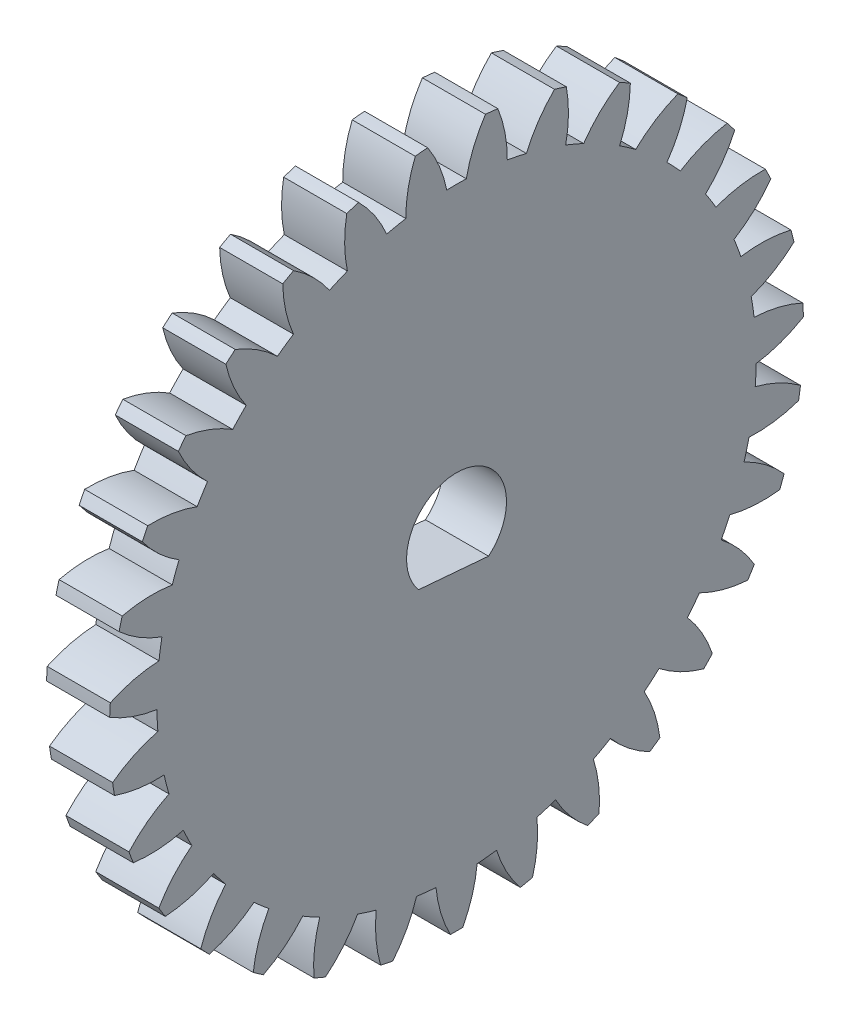
SolidWorks part; units mm, degrees
ref_plane "Plane1" through (0, 0, 0) normal (0, 0, 1) x (1, 0, 0)
ref_plane "Plane2" through (0, 0, 0) normal (0, 1, 0) x (1, 0, 0)
ref_plane "Plane3" through (0, 0, 0) normal (1, 0, 0) x (0, 0, -1)
sketch "HoldingSke" plane through (0, 0, 0) normal (0, 1, 0) x (1, 0, 0)
  line L0 (0, 0) -> (0.8572, -0.515)
  line L1 (-15, 0) -> (100, 0) construction
  line L2 (0, 0) -> (-2.1039, 2.3779)
  line L3 (0, 0) -> (-11.863, 4.5341)
  line L4 (0, 0) -> (7.4025, 4.4479)
  line L5 (0, 0) -> (-46.8476, -17.4728)
  line L6 (0, 0) -> (-1.6579, -1.1186)
  line L7 (-2.1039, 2.3779) -> (8.6586, 51.2059)
  line L8 (-76.2, 54.61) -> (-76.1, 54.61)
  line L9 (-71.009, 38.7566) -> (-53.1078, 45.2721)
  line L10 (-76.2, 71.12) -> (104.1128, 71.12)
  line L11 (0, 0) -> (-2, 0)
  line L12 (-76.2, 101.6) -> (-76.162, 101.6)
  line L13 (24.9733, 27.94) -> (52.9518, 28.4284)
  line L14 (24.9733, 27.94) -> (24.9743, 27.94)
  line L15 (24.9733, 27.94) -> (100.4006, 29.5858)
  line L16 (-63.627, -1) -> (-12.827, -1)
  circle A0 centre (0, 0) radius 0.5
  circle A1 centre (0, 0) radius 14.249
  circle A2 centre (0, 0) radius 37.5
  circle A3 centre (0, 0) radius 0.5
  dimension "MHD" = 28.498
  dimension "Hub_dia" = 75
  dimension "Bore" = 1
  dimension "MBD" = 1
  dimension "Num_teeth" = 31
  dimension "Pitch" = 1
  dimension "Overall_len" = 50
  dimension "Show_teeth" = 31
  dimension "Thickness" = 2
  dimension "OAL" = 50.0001
  dimension "T_dim" = 0.1
  dimension "Ap" = 20
  dimension "H" = 19.05
  dimension "Pitch_radius" = 180.3128
  dimension "Width" = 2
  dimension "Backlash" = 0.038
  dimension "Addendum_fac" = 1
  dimension "Dedendum_fac" = 1.25
  dimension "Clearance_fac" = 0.25
  dimension "Dedendum_add" = 0.001
  dimension "Module" = 1
sketch "BasProSke" plane through (0, 0, 0) normal (0, 1, 0) x (1, 0, 0)
  line L0 (-10, 0) -> (60, 0) construction
  line L1 (0, 0) -> (0, 16.5)
  line L2 (0, 0) -> (2, 0)
  line L3 (2, 0) -> (2, 16.5)
  line L4 (2, 16.5) -> (0, 16.5)
  dimension "Thickness" = 2
  dimension "Diameter" = 33
revolve "Base-Revolve" add sketch "BasProSke" angle 360 about L0
sketch "TooCutSke" plane through (0, 0, 0) normal (1, 0, 0) x (0, 0, -1)
  line L1 (0, 0) -> (0, 107) construction
  line L2 (0, 0) -> (-0.8515, 15.4766) construction
  line L3 (0, 0) -> (-3.1328, 30.8078) construction
  line L4 (-0.8515, 15.4766) -> (-1.5664, 15.4039) construction
  arc A0 (0.4642, 14.2414) -> (-0.4642, 14.2414) centre (0, 0) ccw
  arc A1 (1.3919, 16.4667) -> (-1.3919, 16.4667) centre (0, 0) ccw
  circle A2 centre (0, 0) radius 15.5 construction
  circle A3 centre (0, 0) radius 14.5652 construction
  arc A4 (-0.4642, 14.2414) -> (-1.3919, 16.4667) centre (-6.5414, 13.0137) ccw
  arc A5 (1.3919, 16.4667) -> (0.4642, 14.2414) centre (6.5414, 13.0137) ccw
  dimension "Root_dia" = 28.498
  dimension "Overcut_dia" = 33.0508
  dimension "Pitch_dia" = 31
  dimension "Base_dia" = 29.1305
  dimension "Flank_rad" = 6.2
  dimension "Half_ang" = 5.806
  dimension "Half_CT" = 0.7186
extrude "ToothCut" cut sketch "TooCutSke" along normal through all
fillet "Breaks" [suppressed] radius 0.02 tangent propagation no
fillet "RootFillets" [suppressed] radius 0.251
pattern_circular "TeethCuts" count 31 every 11.613 about axis through (-10, 0, 0) along (1, 0, 0) of "ToothCut", "RootFillets", "Breaks"
sketch "HubNeaOneSke" plane through (0, 0, 0) normal (-1, 0, 0) x (0, 0, 1)
  circle A0 centre (0, 0) radius 14.249
  dimension "Diameter" = 28.498
extrude "HubNearOne" [suppressed] add sketch "HubNeaOneSke" along normal blind 48.0001
sketch "HubNeaBotSke" plane through (0, 0, 0) normal (-1, 0, 0) x (0, 0, 1)
  circle A0 centre (0, 0) radius 14.249
  dimension "Diameter" = 28.498
extrude "HubNearBoth" [suppressed] add sketch "HubNeaBotSke" along normal blind 24
ref_plane "FarPln" through (2, 0, 0) normal (1, 0, 0) x (0, 0, -1)
sketch "HubFarSke" plane through (2, 0, 0) normal (1, 0, 0) x (0, 0, -1)
  circle A0 centre (0, 0) radius 14.249
  dimension "Diameter" = 28.498
extrude "HubFar" [suppressed] add sketch "HubFarSke" along normal blind 24
sketch "BorSke" plane through (0, 0, 0) normal (1, 0, 0) x (0, 0, -1)
  line L0 (-1.806, -1.5423) -> (1.5211, -1.824)
  arc A0 (-1.806, -1.5423) -> (1.5211, -1.824) centre (0, 0) cw
  dimension "D2" = 2.375
  dimension "D1" = 3.339
extrude "Bore" cut sketch "BorSke" along normal mid plane 100.0001
sketch "KeySke" plane through (0, 0, 0) normal (1, 0, 0) x (0, 0, -1)
  line L0 (-0.05, 0) -> (-0.05, 0.6)
  line L1 (-0.05, 0.6) -> (0.05, 0.6)
  line L2 (0.05, 0.6) -> (0.05, 0)
  line L3 (0, 0) -> (0, 34) construction
  line L4 (-0.05, 0) -> (0.05, 0)
  dimension "Offset" = 0.6
extrude "Keyway" [suppressed] cut sketch "KeySke" along normal mid plane 100.0001
pattern_circular "Keyway2" [suppressed] count 2 every 90 about axis through (-10, 0, 0) along (1, 0, 0) reverse direction yes
scale "Scale1" scale about centroid uniform scaling no x scale factor 1.5 y scale factor 1 z scale factor 1
equation "' \"Module@HoldingSke\" = 6.35"
equation "' \"Num_teeth@HoldingSke\" = 12"
equation "' \"Ap@HoldingSke\" =  20"
equation "' \"Ap@HoldingSke\" = 20"
equation "' \"Width@HoldingSke\" = 0.5 * 25.4"
equation "' \"Hub_dia@HoldingSke\"= 1 * 25.4"
equation "' \"Hub_dia@HoldingSke\" = 1 * 25.4"
equation "' \"Overall_len@HoldingSke\" = 1.0 * 25.4"
equation "' \"Bore@HoldingSke\" = 0.75 * 25.4"
equation "' \"T_dim@HoldingSke\" = 0.1 * 25.4"
equation "' \"Width@KeySke\" = 0.25 * 25.4"
equation "' \"Show_teeth@HoldingSke\" = 13"
equation "' \"Backlash@HoldingSke\" = 0.009 * 25.4"
equation "' \"Addendum_fac@HoldingSke\" = 1.0"
equation "' \"Dedendum_fac@HoldingSke\" = 1.25"
equation "' \"Dedendum_add@HoldingSke\" = 0.00005 * 25.4"
equation "' \"Clearance_fac@HoldingSke\" = 0.25"
equation "\"Pitch@HoldingSke\" = 1 / \"Module@HoldingSke\""
equation "\"Overcut_dia@TooCutSke\" = (\"Num_teeth@HoldingSke\" + 2 * \"Addendum_fac@HoldingSke\") / \"Pitch@HoldingSke\" + 0.002 * 25.4"
equation "\"Pitch_dia@TooCutSke\" = \"Num_teeth@HoldingSke\" / \"Pitch@HoldingSke\""
equation "\"Base_dia@TooCutSke\" = \"Num_teeth@HoldingSke\" / \"Pitch@HoldingSke\" * cos((\"Ap@HoldingSke\"  * 3.14159265 / 180))"
equation "\"Root_dia@TooCutSke\" = (\"Num_teeth@HoldingSke\" + 2) / \"Pitch@HoldingSke\" - 2 * (\"Addendum_fac@HoldingSke\" + \"Dedendum_fac@HoldingSke\") / \"Pitch@HoldingSke\" - \"Dedendum_add@HoldingSke\" * 2"
equation "\"Half_ang@TooCutSke\" = 180 / \"Num_teeth@HoldingSke\""
equation "\"Half_CT@TooCutSke\" = \"Num_teeth@HoldingSke\" / \"Pitch@HoldingSke\" * sin((3.14159265 / 2 / \"Num_teeth@HoldingSke\")) / 2 - 7 * \"Backlash@HoldingSke\" / 4"
equation "\"Flank_rad@TooCutSke\" = \"Num_teeth@HoldingSke\" / \"Pitch@HoldingSke\" / 5"
equation "\"Radius@RootFillets\" = \"Clearance_fac@HoldingSke\" / \"Pitch@HoldingSke\" + \"Dedendum_add@HoldingSke\""
equation "\"Break_rad@Breaks\" = 0.02 / \"Pitch@HoldingSke\""
equation "\"Thickness@HoldingSke\" = \"Width@HoldingSke\""
equation "\"OAL@HoldingSke\" = \"Thickness@HoldingSke\""
equation "\"MHD@HoldingSke\" = (\"Num_teeth@HoldingSke\" + 2) / \"Pitch@HoldingSke\" - 2 * (\"Addendum_fac@HoldingSke\" + \"Dedendum_fac@HoldingSke\")  / \"Pitch@HoldingSke\" - \"Dedendum_add@HoldingSke\" * 2"
equation "\"MBD@HoldingSke\" = (\"Num_teeth@HoldingSke\" + 2) / \"Pitch@HoldingSke\" - 2 * (\"Addendum_fac@HoldingSke\" + \"Dedendum_fac@HoldingSke\")  / \"Pitch@HoldingSke\" - \"Dedendum_add@HoldingSke\" * 2 - 0.002 * 25.4"
equation "\"MHD@HoldingSke\" = ((sgn( \"MHD@HoldingSke\" - \"Hub_dia@HoldingSke\" )-1)*( \"MHD@HoldingSke\" - \"Hub_dia@HoldingSke\" ))/-2+ \"Hub_dia@HoldingSke\""
equation "\"MBD@HoldingSke\" = ((sgn( \"MBD@HoldingSke\" - \"Bore@HoldingSke\" )-1)*( \"MBD@HoldingSke\" - \"Bore@HoldingSke\" ))/-2+ \"Bore@HoldingSke\""
equation "\"OAL@HoldingSke\" = ((sgn( \"OAL@HoldingSke\" - \"Overall_len@HoldingSke\" )+1)*( \"OAL@HoldingSke\" - \"Overall_len@HoldingSke\" ))/2 + \"Overall_len@HoldingSke\" + 0.000002 * 25.4"
equation "\"Num_teeth@TeethCuts\" = int( \"Show_teeth@HoldingSke\" ) + 1"
equation "\"Num_teeth@TeethCuts\" = ((sgn( \"Num_teeth@TeethCuts\" - \"Num_teeth@HoldingSke\" )-1)*( \"Num_teeth@TeethCuts\" - \"Num_teeth@HoldingSke\" ))/-2+ \"Num_teeth@HoldingSke\""
equation "\"Num_teeth@TeethCuts\" = ((sgn( \"Num_teeth@TeethCuts\" - 2.0)+1)*( \"Num_teeth@TeethCuts\" - 2.0))/2 +2.0"
equation "\"Angle@TeethCuts\" = 360.0 / \"Num_teeth@HoldingSke\""
equation "\"Diameter@BasProSke\" = (\"Num_teeth@HoldingSke\" + 2 * \"Addendum_fac@HoldingSke\") / \"Pitch@HoldingSke\""
equation "\"Thickness@BasProSke\"  = \"Thickness@HoldingSke\""
equation "' \"Fillet_rad@BasProSke\" =  \"Thickness@HoldingSke\" * 0.05"
equation "' \"Fillet_rad@BasProSke\" = \"Thickness@HoldingSke\" * 0.05"
equation "\"MHD@HoldingSke\" = ((sgn( \"MHD@HoldingSke\" - \"Root_dia@TooCutSke\" )-1)*( \"MHD@HoldingSke\" - \"Root_dia@TooCutSke\" ))/-2+ \"Root_dia@TooCutSke\""
equation "\"Diameter@HubNeaOneSke\" = \"MHD@HoldingSke\""
equation "\"Length@HubNearOne\" = \"OAL@HoldingSke\" - \"Thickness@BasProSke\""
equation "\"Diameter@HubNeaBotSke\" = \"MHD@HoldingSke\""
equation "\"Length@HubNearBoth\" = ( \"OAL@HoldingSke\" - \"Thickness@BasProSke\" ) / 2.0"
equation "\"Thickness@FarPln\" = \"Thickness@BasProSke\""
equation "\"Diameter@HubFarSke\" = \"MHD@HoldingSke\""
equation "\"Length@HubFar\" = ( \"OAL@HoldingSke\" - \"Thickness@BasProSke\" ) / 2.0"
equation "\"D1@Bore\" = \"OAL@HoldingSke\" * 2.0"
equation "\"D1@Keyway\" = \"OAL@HoldingSke\" * 2.0"
equation "\"Offset@KeySke\" = \"T_dim@HoldingSke\" + \"MBD@HoldingSke\" / 2.0"
equation "\"D1@BorSke\"=3.339"
